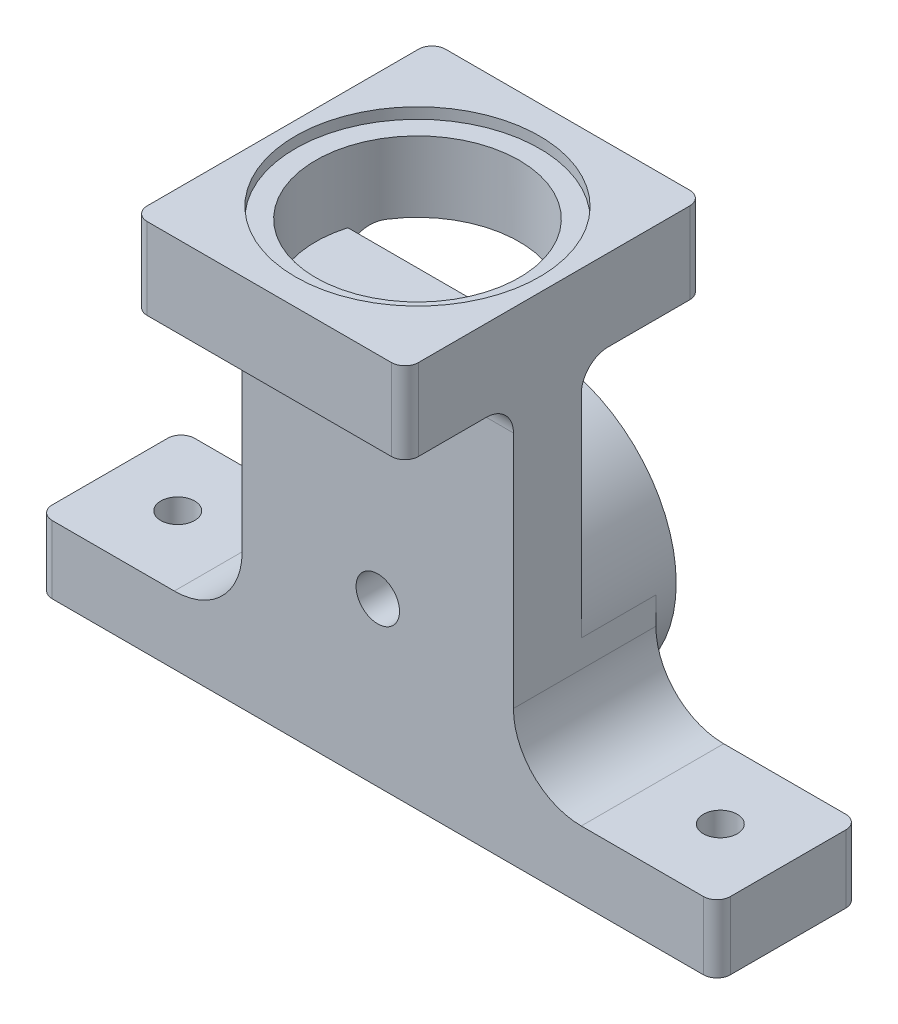
SolidWorks part; units mm, degrees
ref_plane "前视基准面" through (0, 0, 0) normal (0, 0, 1) x (1, 0, 0)
ref_plane "上视基准面" through (0, 0, 0) normal (0, 1, 0) x (1, 0, 0)
ref_plane "右视基准面" through (0, 0, 0) normal (1, 0, 0) x (0, 0, -1)
sketch "草图1" plane through (0, 0, 0) normal (0, 0, 1) x (1, 0, 0)
  circle A0 centre (0, 0) radius 5
  circle A1 centre (0, 0) radius 10
  dimension "D1" = 10
  dimension "D2" = 20
extrude "凸台-拉伸1" add sketch "草图1" along normal blind 7
sketch "草图2" plane through (0, 0, 7) normal (0, 0, 1) x (1, 0, 0)
  circle A0 centre (0, 0) radius 10
  circle A1 centre (0, 0) radius 10 construction
extrude "凸台-拉伸2" add sketch "草图2" along normal blind 5
sketch "草图3" plane through (0, 0, 12) normal (0, 0, 1) x (1, 0, 0)
  line L0 (0, 0) -> (0, -52.479) construction
  line L2 (-10, -12) -> (10, -12)
  line L3 (-10, -12) -> (-10, 0)
  line L4 (-10, 0) -> (10, 0)
  line L5 (10, -12) -> (10, 0)
  line L6 (-10, -12) -> (10, 0) construction
  line L7 (-10, 0) -> (10, -12) construction
  circle A0 centre (0, 0) radius 10 construction
  point P3 (0, -6)
  dimension "D1" = 12
extrude "凸台-拉伸3" add sketch "草图3" against normal blind 5
sketch "草图4" plane through (0, 0, 7) normal (0, 0, -1) x (-1, 0, 0)
  line L0 (-10, 0) -> (-10, -12)
  line L1 (-10, -12) -> (10, -12)
  line L2 (10, -12) -> (10, 0)
  arc A0 (-10, 0) -> (10, 0) centre (0, 0) ccw
  arc A1 (-10, 0) -> (10, 0) centre (0, 0) ccw construction
  arc A2 (10, 0) -> (-10, 0) centre (0, 0) ccw construction
extrude "凸台-拉伸4" add sketch "草图4" along normal blind 5.5
sketch "草图5" plane through (0, -12, 0) normal (0, -1, 0) x (1, 0, 0)
  line L0 (0, 12) -> (0, 1.5) construction
  line L1 (-10, 12) -> (10, 12) construction
  line L2 (10, 1.5) -> (-10, 1.5) construction
  line L4 (-25, 1.5) -> (25, 1.5)
  line L5 (-25, 1.5) -> (-25, 12)
  line L6 (-25, 12) -> (25, 12)
  line L7 (25, 1.5) -> (25, 12)
  line L8 (-25, 1.5) -> (25, 12) construction
  line L9 (-25, 12) -> (25, 1.5) construction
  point P6 (0, 6.75)
  dimension "D1" = 50
extrude "凸台-拉伸5" add sketch "草图5" against normal blind 5
sketch "草图6" plane through (0, 0, 7) normal (0, 0, -1) x (-1, 0, 0)
  circle A0 centre (0, 0) radius 1.6
  dimension "D1" = 3.2
extrude "切除-拉伸1" cut sketch "草图6" against normal up to next
sketch "草图7" plane through (0, -12, 0) normal (0, -1, 0) x (1, 0, 0)
  line L0 (-25, 6.75) -> (25, 6.75) construction
  line L1 (-25, 12) -> (-25, 1.5) construction
  line L2 (25, 1.5) -> (25, 12) construction
  line L3 (0, 12) -> (0, 1.5) construction
  line L4 (-25, 12) -> (25, 12) construction
  line L5 (-10, 1.5) -> (10, 1.5) construction
  circle A0 centre (-20, 6.75) radius 1.25
  circle A1 centre (-7.5, 6.75) radius 1.25
  circle A2 centre (20, 6.75) radius 1.25
  circle A3 centre (7.5, 6.75) radius 1.25
  dimension "D1" = 15
  dimension "D2" = 40
  dimension "D3" = 2.5
extrude "切除-拉伸2" cut sketch "草图7" against normal blind 10
cosmetic thread "装饰螺纹线1" parameters "D1"=5, "D2"=3
cosmetic thread "装饰螺纹线2" parameters "D1"=5, "D2"=3
cosmetic thread "装饰螺纹线3" parameters "D1"=5, "D2"=3
cosmetic thread "装饰螺纹线4" parameters "D1"=5, "D2"=3
fillet "圆角1" radius 1 4 edges at (25, -9.5, 1.5) (25, -9.5, 12) (-25, -9.5, 12) (-25, -9.5, 1.5)
fillet "圆角2" radius 5 2 edges at (10, -7, 6.75) (-10, -7, 6.75)
sketch "草图8" plane through (0, 0, 12) normal (0, 0, 1) x (1, 0, 0)
  line L0 (-10, 0) -> (-10, 17.59)
  line L1 (-10, 17.59) -> (10, 17.59)
  line L2 (10, 17.59) -> (10, 0)
  arc A0 (-10, 0) -> (10, 0) centre (0, 0) ccw
  arc A1 (10, 0) -> (-10, 0) centre (0, 0) ccw construction
  arc A2 (10, 0) -> (-10, 0) centre (0, 0) ccw construction
  circle A3 centre (0, 0) radius 1.6
  dimension "D2" = 3.2
  dimension "D1" = 17.59
extrude "凸台-拉伸6" add sketch "草图8" against normal blind 5
sketch "草图9" plane through (0, 17.59, 0) normal (0, 1, 0) x (1, 0, 0)
  line L0 (0, -12) -> (0, -8) construction
  line L1 (10, -12) -> (-10, -12) construction
  line L2 (10, -7) -> (10, -12) construction
  line L3 (-10, -22) -> (10, -22)
  line L4 (-10, -22) -> (-10, 2)
  line L5 (-10, 2) -> (10, 2)
  line L6 (10, -22) -> (10, 2)
  line L7 (-10, -22) -> (10, 2) construction
  line L8 (-10, 2) -> (10, -22) construction
  line L10 (10, -7) -> (-10, -7) construction
  point P5 (0, -10)
  dimension "D1" = 3
  dimension "D2" = 24
extrude "凸台-拉伸7" add sketch "草图9" along normal blind 6
sketch "草图10" plane through (0, 23.59, 0) normal (0, 1, 0) x (1, 0, 0)
  line L0 (10, -22) -> (10, 2) construction
  line L1 (-10, -22) -> (10, -22)
  line L2 (-10, -22) -> (-10, -20)
  line L3 (-10, -20) -> (10, -20)
  line L4 (10, -22) -> (10, -20)
  dimension "D1" = 2
extrude "切除-拉伸3" cut sketch "草图10" against normal up to next
sketch "草图11" plane through (0, 23.59, 0) normal (0, 1, 0) x (1, 0, 0)
  circle A0 centre (0, -9.073) radius 7.5
  dimension "D1" = 15
extrude "切除-拉伸4" cut sketch "草图11" against normal blind 6
sketch "草图12" plane through (0, 23.59, 0) normal (0, 1, 0) x (1, 0, 0)
  circle A0 centre (0, -9.073) radius 9
  dimension "D1" = 18
extrude "切除-拉伸5" cut sketch "草图12" against normal blind 0.8
fillet "圆角3" radius 1 4 edges at (-10, 20.59, -2) (10, 20.59, -2) (10, 20.59, 20) (-10, 20.59, 20)
fillet "圆角4" radius 2 4 edges at (-8.6039, 17.59, 7) (8.6039, 17.59, 7) (8.4526, 17.59, 12) (-8.4526, 17.59, 12)
